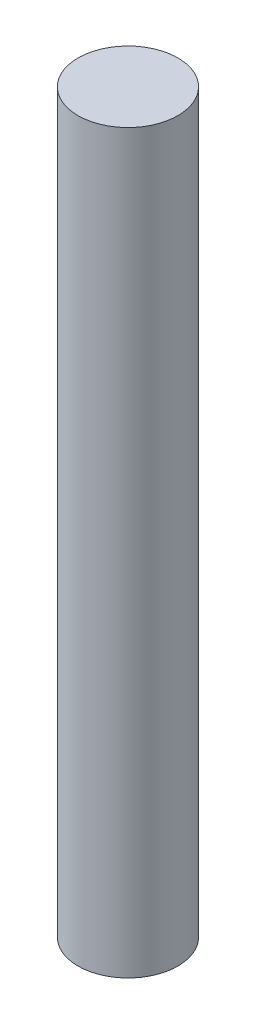
SolidWorks part; units mm, degrees
ref_plane "Front Plane" through (0, 0, 0) normal (0, 0, 1) x (1, 0, 0)
ref_plane "Top Plane" through (0, 0, 0) normal (0, 1, 0) x (1, 0, 0)
ref_plane "Right Plane" through (0, 0, 0) normal (1, 0, 0) x (0, 0, -1)
sketch "Sketch1" plane through (0, 0, 0) normal (0, 1, 0) x (1, 0, 0)
  circle A0 centre (0, 0) radius 27.2
  dimension "D1" = 54.4
extrude "Boss-Extrude1" add sketch "Sketch1" along normal blind 401
equation "\"Motor_Length\" = 401mm"
equation "\"Motor_OD\" = 54.4mm"
equation "\"D1@Sketch1\"=\"Motor_OD\""
equation "\"D1@Boss-Extrude1\"=\"Motor_Length\""
equation "\"Aft_Section_Length\" = 32in"
equation "\"Mid_Coupler_Length\" = 12in"
equation "\"AB_Coupler_OD_Length\"= 1in"
equation "\"AB_Coupling_Section_Length\"= 0.375in"
equation "\"AB_Coupler_Length\"= \"AB_Coupler_OD_Length\" + \"AB_Coupling_Section_Length\" * 2"
equation "\"Cutout_Angle\" = 60"
equation "\"AB_Paddle_Height\" = 0.375in"
equation "\"AB_Coupler_Num_Screws\"= 4"
equation "\"Num_Cutouts\" = 4"
equation "\"AB_Coupler_OD\"= 4.024in"
equation "\"AB_Coupler_ID\"= 3.7in"
equation "\"AB_Coupler_Surface_Diameter\"= 3.899in"
equation "\"AB_Coupling_Screw_Diameter\"= 0.1065in"
equation "\"AB_Central_Bushing_Length\" = 0.75in"
equation "\"Lead_Screw_Dist\" = 2in"
equation "\"Lead_Screw_Diam\" = 0.375in"
equation "\"Lead_Screw_Length\" = \"Mid_Coupler_Length\" + 2*0.375in + 2*0.5in"
equation "\"Paddle_Pin_Offset\" = 0.25in"
equation "\"Paddle_Pin_Radius\" = 2.25*2/3in"
equation "\"Paddle_Gear_OD\" = 3.2in"
equation "\"Fwd_BKHD_From_Top\" = 18in"
equation "\"Body_Tube_OD\"= 4.024in"
equation "\"Body_Tube_ID\"= 3.90in"
equation "\"Coupler_OD\" = 3.899in"
equation "\"Coupler_ID\" = 3.755in"
equation "\"Fwd_Section_Length\" = 20in"
equation "\"Mid_Section_Length\" = 4in"
equation "\"Aft_Upper_Tube_Length\" = 10in"
equation "\"Aft_Lower_Tube_Length\" = 18in"
equation "\"Nosecone_Coupler_Length\" = 5in"
equation "\"Avionics_Bulkhead_Thickness\" = 0.25in"
equation "\"Avionics_Bulkhead_Lip\" = 0.125in"
equation "\"Avionics_Board_Length\" = \"Mid_Coupler_Length\" - 2*\"Avionics_Bulkhead_Lip\""
equation "\"Lead_Screw_Hole_Diam\" = 0.386in"
equation "\"Centering_Ring_Cutout_Dia\"=1.5in"
